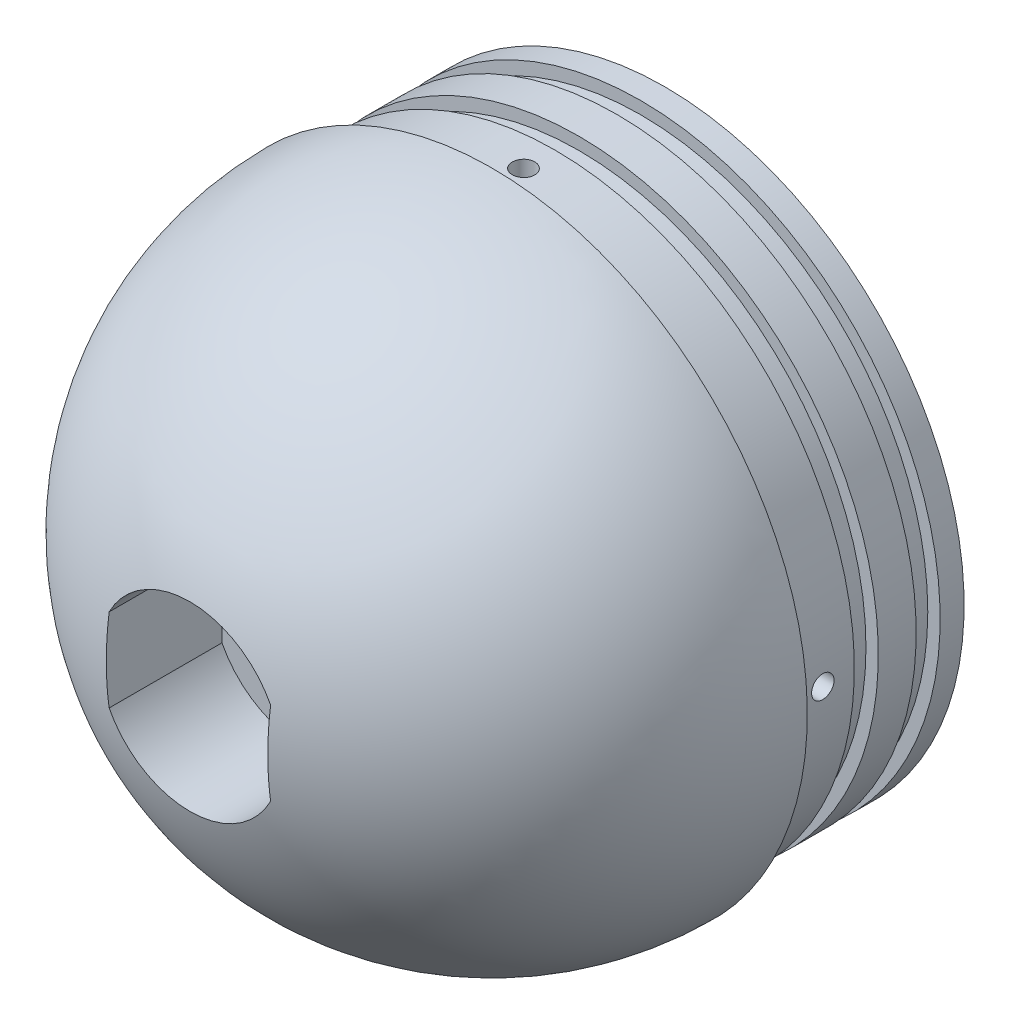
SolidWorks part; units mm, degrees
material "6061-T6 (SS)"
ref_plane "XY" through (0, 0, 0) normal (0, 0, 1) x (1, 0, 0)
ref_plane "XZ" through (0, 0, 0) normal (0, 1, 0) x (1, 0, 0)
ref_plane "YZ" through (0, 0, 0) normal (1, 0, 0) x (0, 0, -1)
ref_axis "X" through (-34.925, 0, 0) along (1, 0, 0)
ref_axis "Y" through (0, -34.925, 0) along (0, 1, 0)
ref_axis "Z" through (0, 0, 50.4955) along (0, 0, -1)
sketch "Sketch2" plane through (0, 0, 0) normal (1, 0, 0) x (0, 0, -1)
  line L2 (-17.399, 30.1371) -> (-11.049, 30.1371)
  line L3 (-11.049, 30.1371) -> (-11.049, 28.8925)
  line L4 (-11.049, 28.8925) -> (-8.636, 28.8925)
  line L5 (-8.636, 28.8925) -> (-8.636, 30.1371)
  line L6 (-8.636, 30.1371) -> (-4.826, 30.1371)
  line L7 (-4.826, 30.1371) -> (-4.826, 28.8925)
  line L8 (-4.826, 28.8925) -> (-2.413, 28.8925)
  line L9 (-2.413, 28.8925) -> (-2.413, 30.1371)
  line L10 (-2.413, 30.1371) -> (0, 30.1371)
  line L11 (0, 30.1371) -> (0, 0)
  line L12 (0, 0) -> (-17.399, 0)
  line L13 (-17.399, 30.1371) -> (-17.399, 0)
  point P0 (0, 0)
  dimension "D1" = 30.1371
  dimension "D2" = 28.8925
  dimension "D3" = 2.413
  dimension "D4" = 3.81
  dimension "D5" = 2.413
  dimension "D7" = 6.35
revolve "Revolve1" add sketch "Sketch2" angle 360 about L12
hole_wizard "#4-40 Tapped Hole1" positions "3DSketch1" profile "Sketch3" tap size "#4-40" standard "ANSI Inch"
sketch3d "3DSketch1"
  line L0 (0, 0, 0) -> (0, 0, 14.224)
  line L1 (0, 0, 14.224) -> (-30.1371, 0, 14.224)
  line L3 (30.1371, 0, 14.224) -> (0, -30.1371, 14.224)
  line L5 (0, -30.1371, 14.224) -> (-30.1371, 0, 14.224)
  line L9 (0, 0, 14.224) -> (0, -30.1371, 14.224)
  line L11 (0, 0, 14.224) -> (30.1371, 0, 14.224)
  line L13 (0, 0, 14.224) -> (0, 30.1371, 14.224)
  line L15 (0, -30.1371, 11.049) -> (0, -30.1371, 17.399)
  line L16 (0, 30.1371, 14.224) -> (-30.1371, 0, 14.224)
  line L18 (30.1371, 0, 14.224) -> (0, 30.1371, 14.224)
  circle A1 centre (0, 0, 11.049) radius 30.1371 construction
  circle A2 centre (0, 0, 17.399) radius 30.1371 construction
  point P5 (0, -30.1371, 14.224)
  point P7 (30.1371, 0, 14.224)
  point P20 (-30.1371, 0, 14.224)
  point P1370 (0, 0, -19.0881)
  point P1373 (0, 0, -12.7381)
  point P1390 (0, 30.1371, 14.224)
cosmetic thread "Hole Thread2" parameters "D1"=5.588, "D2"=2.8448
cosmetic thread "Hole Thread3" parameters "D1"=5.588, "D2"=2.8448
cosmetic thread "Hole Thread5" parameters "D1"=5.588, "D2"=2.8448
cosmetic thread "Hole Thread6" parameters "D1"=5.588, "D2"=2.8448
sketch "Sketch3" plane through (0, -30.1371, 14.224) normal (1, 0, 0) x (0, 0, -1)
  line L0 (0, 0) -> (0, 8.2992)
  line L1 (0, 8.2992) -> (1.1303, 7.62)
  line L2 (1.1303, 7.62) -> (1.1303, 0)
  line L5 (1.1303, 0) -> (0, 0)
  line L10 (0, 8.2992) -> (-1.1303, 7.62) construction
  line L11 (0, -6.35) -> (0, 107.95) construction
  dimension "Tap Drill Dia." = 2.2606
  dimension "Tap Drill Depth" = 7.62
  dimension "Drill Angle" = 118
sketch "Sketch6" plane through (0, 0, 0) normal (0, 1, 0) x (1, 0, 0)
  line L0 (0, -17.399) -> (31.75, -17.399)
  line L1 (-30.1371, -17.399) -> (30.1371, -17.399) construction
  line L2 (0, -17.399) -> (0, -49.149)
  arc A0 (0, -49.149) -> (31.75, -17.399) centre (0, -17.399) ccw
  dimension "D1" = 31.75
revolve "Revolve2" add sketch "Sketch6" angle 360 about L2
ref_plane "Plane1" through (0, 0, 49.149) normal (0, 0, 1) x (1, 0, 0)
sketch "Sketch8" plane through (0, 0, 49.149) normal (0, 0, 1) x (1, 0, 0)
  line L1 (-8.128, 4.1891) -> (8.128, 4.1891) construction
  line L2 (-8.128, 4.1891) -> (-8.128, -4.1891)
  line L3 (-8.128, -4.1891) -> (8.128, -4.1891) construction
  line L4 (8.128, 4.1891) -> (8.128, -4.1891)
  line L5 (-8.128, 4.1891) -> (8.128, -4.1891) construction
  line L6 (-8.128, -4.1891) -> (8.128, 4.1891) construction
  arc A0 (8.128, 4.1891) -> (-8.128, 4.1891) centre (0, 0) ccw
  arc A1 (-8.128, -4.1891) -> (8.128, -4.1891) centre (0, 0) ccw
  point P7 (-6.0937, -6.473)
  dimension "D1" = 18.288
  dimension "D2" = 16.256
extrude "Cut-Extrude1" cut sketch "Sketch8" against normal blind 12.7
sketch "Sketch9" plane through (0, 0, 36.449) normal (0, 0, 1) x (1, 0, 0)
  circle A0 centre (0, 0) radius 5.1
  dimension "D1" = 10.2
extrude "Cut-Extrude2" cut sketch "Sketch9" against normal through all
sketch "Sketch10" plane through (0, 0, 0) normal (0, 0, -1) x (-1, 0, 0)
  circle A0 centre (0, 0) radius 19.9478
extrude "Cut-Extrude3" cut sketch "Sketch10" against normal offset from surface (28.449 mm away) 8 up to face at (5.1, 0, 36.449)
